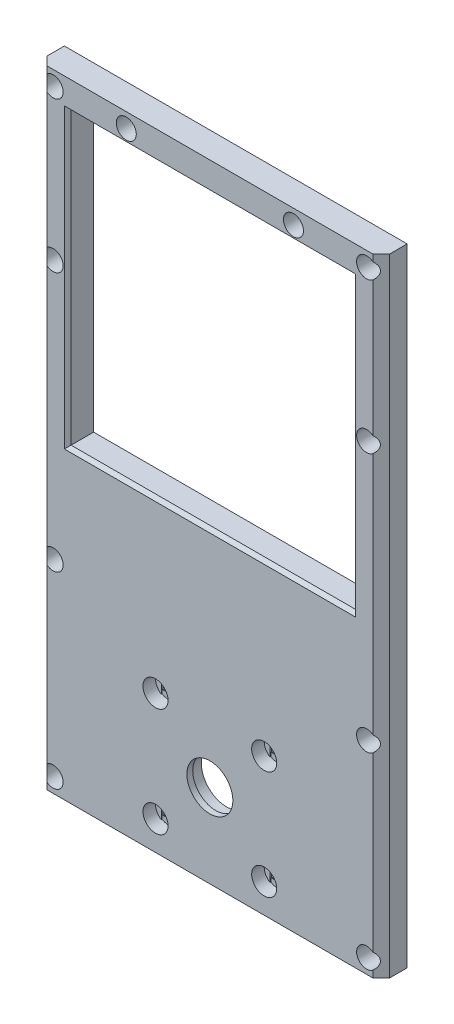
SolidWorks part; units mm, degrees
ref_plane "Front Plane" through (0, 0, 0) normal (0, 0, 1) x (1, 0, 0)
ref_plane "Top Plane" through (0, 0, 0) normal (0, 1, 0) x (1, 0, 0)
ref_plane "Right Plane" through (0, 0, 0) normal (1, 0, 0) x (0, 0, -1)
sketch "Sketch1" plane through (0, 0, 0) normal (0, 0, 1) x (1, 0, 0)
  line L1 (-41, -75) -> (41, -75)
  line L2 (-41, -75) -> (-41, 75)
  line L3 (-41, 75) -> (41, 75)
  line L4 (41, -75) -> (41, 75)
  line L5 (-41, -75) -> (41, 75) construction
  line L6 (-41, 75) -> (41, -75) construction
  line L7 (-34, -68) -> (34, -68)
  line L8 (-34, -68) -> (-34, 68)
  line L9 (-34, 68) -> (34, 68)
  line L10 (34, -68) -> (34, 68)
  line L11 (-34, -68) -> (34, 68) construction
  line L12 (-34, 68) -> (34, -68) construction
  point P0 (0, 0)
  point P6 (0, 0)
  dimension "D1" = 150
  dimension "D2" = 82
  dimension "D3" = 7
  dimension "D4" = 7
extrude "Boss-Extrude1" add sketch "Sketch1" along normal blind 7
sketch "Sketch2" plane through (0, 0, 7) normal (0, 0, 1) x (1, 0, 0)
  line L0 (34, -68) -> (34, 68) construction
  line L1 (-34, -68) -> (34, -68)
  line L2 (-34, -68) -> (-34, -32)
  line L3 (-34, -32) -> (34, -32)
  line L4 (34, -68) -> (34, -32)
  dimension "D1" = 36
extrude "Boss-Extrude2" add sketch "Sketch2" against normal up to surface (7 mm away) up to face at (0, 0, 0)
sketch "Sketch3" plane through (0, 0, 0) normal (0, 0, -1) x (-1, 0, 0)
  line L0 (0, -75) -> (0, -55) construction
  line L1 (41, -75) -> (-41, -75) construction
  circle A0 centre (0, -55) radius 5.5
  dimension "D1" = 11
  dimension "D2" = 20
extrude "Cut-Extrude1" cut sketch "Sketch3" against normal through all
sketch "Sketch4" plane through (0, 0, 0) normal (0, 0, -1) x (-1, 0, 0)
  circle A0 centre (0, -55) radius 6.05
  dimension "D1" = 12.1
extrude "Cut-Extrude2" cut sketch "Sketch4" against normal offset from surface (5.6 mm away) 1.4 up to face at (-5.5, -55, 7)
sketch "Sketch5" plane through (0, 0, 0) normal (0, 0, -1) x (-1, 0, 0)
  circle A0 centre (0, -55) radius 11
  dimension "D1" = 22
extrude "Cut-Extrude3" cut sketch "Sketch5" against normal offset from surface (3 mm away) 2.6 up to face at (-6.05, -55, 5.6)
sketch "Sketch6" plane through (0, 0, 0) normal (0, 0, -1) x (-1, 0, 0)
  line L1 (-13, -68) -> (13, -68) construction
  line L2 (-13, -68) -> (-13, -42) construction
  line L3 (-13, -42) -> (13, -42) construction
  line L4 (13, -68) -> (13, -42) construction
  line L5 (-13, -68) -> (13, -42) construction
  line L6 (-13, -42) -> (13, -68) construction
  circle A0 centre (-13, -42) radius 1.6
  circle A1 centre (13, -42) radius 1.6
  circle A2 centre (13, -68) radius 1.6
  circle A3 centre (-13, -68) radius 1.6
  point P0 (0, -55)
  dimension "D2" = 3.2
  dimension "D1" = 26
extrude "Cut-Extrude4" cut sketch "Sketch6" against normal through all
sketch "Sketch7" plane through (0, 0, 0) normal (0, 0, -1) x (-1, 0, 0)
  line L1 (-25, -74) -> (25, -74)
  line L2 (-25, -74) -> (-25, -36)
  line L3 (-25, -36) -> (25, -36)
  line L4 (25, -74) -> (25, -36)
  line L5 (-25, -74) -> (25, -36) construction
  line L6 (-25, -36) -> (25, -74) construction
  point P0 (0, -55)
  dimension "D1" = 50
  dimension "D2" = 38
extrude "Cut-Extrude5" cut sketch "Sketch7" against normal blind 1
sketch "Sketch8" plane through (0, 0, 7) normal (0, 0, 1) x (1, 0, 0)
  circle A0 centre (-13, -42) radius 3
  circle A1 centre (13, -42) radius 3
  circle A2 centre (13, -68) radius 3
  circle A3 centre (-13, -68) radius 3
  dimension "D1" = 6
extrude "Cut-Extrude6" cut sketch "Sketch8" against normal blind 3
sketch "Sketch9" plane through (0, 0, 7) normal (0, 0, 1) x (1, 0, 0)
  line L0 (-41, 75) -> (-41, -75) construction
  line L1 (-37.5, -71.5) -> (37.5, -71.5) construction
  line L2 (-37.5, -71.5) -> (-37.5, 71.5) construction
  line L3 (-37.5, 71.5) -> (37.5, 71.5) construction
  line L4 (37.5, -71.5) -> (37.5, 71.5) construction
  line L5 (-37.5, -71.5) -> (37.5, 71.5) construction
  line L6 (-37.5, 71.5) -> (37.5, -71.5) construction
  line L7 (41, 75) -> (-41, 75) construction
  circle A0 centre (-37.5, 71.5) radius 1.35
  circle A1 centre (37.5, 71.5) radius 1.35
  circle A4 centre (-37.5, -71.5) radius 1.35
  circle A5 centre (37.5, -71.5) radius 1.35
  circle A6 centre (-37.5, 35.5) radius 1.35
  circle A7 centre (37.5, 35.5) radius 1.35
  circle A8 centre (37.5, -26.5) radius 1.35
  circle A9 centre (-37.5, -26.5) radius 1.35
  point P0 (0, 0)
  dimension "D3" = 2.7
  dimension "D1" = 3.5
  dimension "D2" = 3.5
  dimension "D4" = 45
  dimension "D5" = 36
extrude "Cut-Extrude7" cut sketch "Sketch9" against normal through all
sketch "Sketch10" plane through (0, 0, 7) normal (0, 0, 1) x (1, 0, 0)
  circle A0 centre (-37.5, 71.5) radius 2.4
  circle A1 centre (37.5, 35.5) radius 2.4
  circle A2 centre (-37.5, 35.5) radius 2.4
  circle A3 centre (37.5, 71.5) radius 2.4
  circle A4 centre (-37.5, -71.5) radius 2.4
  circle A5 centre (37.5, -71.5) radius 2.4
  circle A6 centre (-37.5, -26.5) radius 2.4
  circle A7 centre (37.5, -26.5) radius 2.4
  dimension "D1" = 4.8
extrude "Cut-Extrude8" cut sketch "Sketch10" against normal blind 5
chamfer "Chamfer1" distance 2 angle 45 2 edges at (-41, 0, 7) (41, 0, 7)
sketch "Sketch11" plane through (0, 0, 7) normal (0, 0, 1) x (1, 0, 0)
  line L0 (34, -32) -> (34, 68) construction
  line L1 (-34, -32) -> (34, -32)
  line L2 (-34, -32) -> (-34, -1.5)
  line L3 (-34, -1.5) -> (34, -1.5)
  line L4 (34, -32) -> (34, -1.5)
  line L5 (-39, -75) -> (39, -75) construction
  dimension "D1" = 73.5
extrude "Boss-Extrude3" add sketch "Sketch11" against normal up to surface (7 mm away) up to face at (-36.15, -71.5, 0)
sketch "Sketch12" plane through (0, 0, 7) normal (0, 0, 1) x (1, 0, 0)
  line L0 (-37.5, 71.5) -> (37.5, 71.5) construction
  line L1 (-20, 71.5) -> (20, 71.5) construction
  circle A0 centre (-20, 71.5) radius 1.35
  circle A1 centre (20, 71.5) radius 1.35
  circle A2 centre (-37.5, 71.5) radius 1.35 construction
  point P7 (0, 71.5)
  dimension "D1" = 40
extrude "Cut-Extrude9" cut sketch "Sketch12" against normal through all
sketch "Sketch13" plane through (0, 0, 7) normal (0, 0, 1) x (1, 0, 0)
  circle A0 centre (-20, 71.5) radius 2.4
  circle A1 centre (20, 71.5) radius 2.4
  circle A2 centre (-37.5, 71.5) radius 2.4 construction
extrude "Cut-Extrude10" cut sketch "Sketch13" against normal up to surface (5 mm away) up to face at (-35.1, 71.5, 2)
chamfer "Chamfer2" distance 0.8 angle 45 12 edges at (0, -75, 0) (-41, 0, 0) (0, 75, 0) (41, 0, 0) (34, 33.25, 7) (0, 68, 7) (-34, 33.25, 7) (0, -1.5, 7) (-34, 33.25, 0) (0, 68, 0) (34, 33.25, 0) (0, -1.5, 0)
sketch "Sketch14" plane through (0, 0, 2) normal (0, 0, 1) x (1, 0, 0)
  line L2 (-38.85, -28.4843) -> (-38.85, -24.5157)
  line L4 (-36.15, -28.4843) -> (-36.15, -24.5157)
  line L5 (-38.85, -28.4843) -> (-36.15, -24.5157) construction
  line L6 (-38.85, -24.5157) -> (-36.15, -28.4843) construction
  line L14 (-38.85, -73.4843) -> (-38.85, -69.5157)
  line L16 (-36.15, -73.4843) -> (-36.15, -69.5157)
  line L17 (-38.85, -73.4843) -> (-36.15, -69.5157) construction
  line L18 (-38.85, -69.5157) -> (-36.15, -73.4843) construction
  line L26 (-38.85, 33.5157) -> (-38.85, 37.4843)
  line L28 (-36.15, 33.5157) -> (-36.15, 37.4843)
  line L29 (-38.85, 33.5157) -> (-36.15, 37.4843) construction
  line L30 (-38.85, 37.4843) -> (-36.15, 33.5157) construction
  line L32 (-21.35, 69.5157) -> (-21.35, 73.4843)
  line L34 (-18.65, 69.5157) -> (-18.65, 73.4843)
  line L35 (-21.35, 69.5157) -> (-18.65, 73.4843) construction
  line L36 (-21.35, 73.4843) -> (-18.65, 69.5157) construction
  line L38 (-38.85, 69.5157) -> (-38.85, 73.4843)
  line L40 (-36.15, 69.5157) -> (-36.15, 73.4843)
  line L41 (-38.85, 69.5157) -> (-36.15, 73.4843) construction
  line L42 (-38.85, 73.4843) -> (-36.15, 69.5157) construction
  arc A0 (-39, -28.3735) -> (-39, -24.6265) centre (-37.5, -26.5) ccw construction
  circle A2 centre (-37.5, -71.5) radius 2.4 construction
  circle A4 centre (-37.5, 35.5) radius 2.4 construction
  circle A5 centre (-20, 71.5) radius 2.4 construction
  circle A6 centre (-37.5, 71.5) radius 2.4 construction
  circle A7 centre (-37.5, 71.5) radius 1.35 construction
  circle A8 centre (-20, 71.5) radius 1.35 construction
  circle A9 centre (-37.5, 35.5) radius 1.35 construction
  circle A10 centre (-37.5, -26.5) radius 1.35 construction
  circle A12 centre (-37.5, -71.5) radius 1.35 construction
  arc A16 (-21.35, 69.5157) -> (-18.65, 69.5157) centre (-20, 71.5) ccw
  arc A17 (-36.15, 73.4843) -> (-38.85, 73.4843) centre (-37.5, 71.5) ccw
  arc A18 (-36.15, 37.4843) -> (-38.85, 37.4843) centre (-37.5, 35.5) ccw
  arc A20 (-38.85, -28.4843) -> (-36.15, -28.4843) centre (-37.5, -26.5) ccw
  arc A22 (-36.15, -69.5157) -> (-38.85, -69.5157) centre (-37.5, -71.5) ccw
  arc A23 (-38.85, 69.5157) -> (-36.15, 69.5157) centre (-37.5, 71.5) ccw
  arc A24 (-18.65, 73.4843) -> (-21.35, 73.4843) centre (-20, 71.5) ccw
  arc A25 (-38.85, 33.5157) -> (-36.15, 33.5157) centre (-37.5, 35.5) ccw
  arc A26 (-36.15, -24.5157) -> (-38.85, -24.5157) centre (-37.5, -26.5) ccw
  arc A29 (-38.85, -73.4843) -> (-36.15, -73.4843) centre (-37.5, -71.5) ccw
  point P0 (-37.5, -26.5)
  point P17 (-37.5, -71.5)
  point P33 (-37.5, 35.5)
  point P41 (-20, 71.5)
  point P49 (-37.5, 71.5)
extrude "Cut-Extrude11" cut sketch "Sketch14" against normal blind 0.2
sketch "Sketch15" plane through (0, 0, 1.8) normal (0, 0, 1) x (1, 0, 0)
  line L0 (-36.15, -71.5) -> (-36.15, -69.5157) construction
  line L1 (-38.85, -72.85) -> (-36.15, -72.85)
  line L2 (-38.85, -72.85) -> (-38.85, -70.15)
  line L3 (-38.85, -70.15) -> (-36.15, -70.15)
  line L4 (-36.15, -72.85) -> (-36.15, -70.15)
  line L5 (-38.85, -72.85) -> (-36.15, -70.15) construction
  line L6 (-38.85, -70.15) -> (-36.15, -72.85) construction
  line L7 (-36.15, 35.5) -> (-36.15, 37.4843) construction
  line L8 (-38.85, -27.85) -> (-36.15, -27.85)
  line L9 (-38.85, -27.85) -> (-38.85, -25.15)
  line L10 (-38.85, -25.15) -> (-36.15, -25.15)
  line L11 (-36.15, -27.85) -> (-36.15, -25.15)
  line L12 (-38.85, -27.85) -> (-36.15, -25.15) construction
  line L13 (-38.85, -25.15) -> (-36.15, -27.85) construction
  line L14 (-38.85, 34.15) -> (-36.15, 34.15)
  line L15 (-38.85, 34.15) -> (-38.85, 36.85)
  line L16 (-38.85, 36.85) -> (-36.15, 36.85)
  line L17 (-36.15, 34.15) -> (-36.15, 36.85)
  line L18 (-38.85, 34.15) -> (-36.15, 36.85) construction
  line L19 (-38.85, 36.85) -> (-36.15, 34.15) construction
  line L20 (-36.15, 69.5157) -> (-36.15, 73.4843) construction
  line L21 (-38.85, 70.15) -> (-36.15, 70.15)
  line L22 (-38.85, 70.15) -> (-38.85, 72.85)
  line L23 (-38.85, 72.85) -> (-36.15, 72.85)
  line L24 (-36.15, 70.15) -> (-36.15, 72.85)
  line L25 (-38.85, 70.15) -> (-36.15, 72.85) construction
  line L26 (-38.85, 72.85) -> (-36.15, 70.15) construction
  line L27 (-18.65, 69.5157) -> (-18.65, 73.4843) construction
  line L28 (-21.35, 70.15) -> (-18.65, 70.15)
  line L29 (-21.35, 70.15) -> (-21.35, 72.85)
  line L30 (-21.35, 72.85) -> (-18.65, 72.85)
  line L31 (-18.65, 70.15) -> (-18.65, 72.85)
  line L32 (-21.35, 70.15) -> (-18.65, 72.85) construction
  line L33 (-21.35, 72.85) -> (-18.65, 70.15) construction
  arc A0 (-36.15, -26.5) -> (-38.85, -26.5) centre (-37.5, -26.5) ccw construction
  arc A1 (-36.15, 35.5) -> (-38.85, 35.5) centre (-37.5, 35.5) ccw construction
  arc A2 (-18.65, 71.5) -> (-21.35, 71.5) centre (-20, 71.5) ccw construction
  arc A3 (-36.15, 71.5) -> (-38.85, 71.5) centre (-37.5, 71.5) ccw construction
  point P0 (-37.5, -71.5)
  point P8 (-37.5, -26.5)
  point P17 (-37.5, 35.5)
  point P28 (-37.5, 71.5)
  point P36 (-20, 71.5)
extrude "Cut-Extrude12" cut sketch "Sketch15" against normal blind 0.2
sketch "Sketch16" plane through (0, 0, 4) normal (0, 0, 1) x (1, 0, 0)
  line L2 (-14.6, -44.5377) -> (-14.6, -39.4623)
  line L4 (-11.4, -44.5377) -> (-11.4, -39.4623)
  line L5 (-14.6, -44.5377) -> (-11.4, -39.4623) construction
  line L6 (-14.6, -39.4623) -> (-11.4, -44.5377) construction
  line L8 (-14.6, -70.5377) -> (-14.6, -65.4623)
  line L10 (-11.4, -70.5377) -> (-11.4, -65.4623)
  line L11 (-14.6, -70.5377) -> (-11.4, -65.4623) construction
  line L12 (-14.6, -65.4623) -> (-11.4, -70.5377) construction
  circle A0 centre (-13, -42) radius 3 construction
  circle A1 centre (-13, -68) radius 3 construction
  circle A2 centre (-13, -68) radius 1.6 construction
  circle A3 centre (-13, -42) radius 1.6 construction
  circle A4 centre (-13, -68) radius 3 construction
  circle A5 centre (-13, -42) radius 3 construction
  arc A6 (-11.4, -65.4623) -> (-14.6, -65.4623) centre (-13, -68) ccw
  arc A7 (-14.6, -44.5377) -> (-11.4, -44.5377) centre (-13, -42) ccw
  arc A8 (-11.4, -39.4623) -> (-14.6, -39.4623) centre (-13, -42) ccw
  arc A9 (-14.6, -70.5377) -> (-11.4, -70.5377) centre (-13, -68) ccw
  point P0 (-13, -42)
  point P8 (-13, -68)
extrude "Cut-Extrude13" cut sketch "Sketch16" against normal blind 0.2
sketch "Sketch17" plane through (0, 0, 3.8) normal (0, 0, 1) x (1, 0, 0)
  line L0 (-11.4, -44.5377) -> (-11.4, -39.4623) construction
  line L1 (-14.6, -43.6) -> (-11.4, -43.6)
  line L2 (-14.6, -43.6) -> (-14.6, -40.4)
  line L3 (-14.6, -40.4) -> (-11.4, -40.4)
  line L4 (-11.4, -43.6) -> (-11.4, -40.4)
  line L5 (-14.6, -43.6) -> (-11.4, -40.4) construction
  line L6 (-14.6, -40.4) -> (-11.4, -43.6) construction
  line L7 (-11.4, -70.5377) -> (-11.4, -65.4623) construction
  line L8 (-14.6, -69.6) -> (-11.4, -69.6)
  line L9 (-14.6, -69.6) -> (-14.6, -66.4)
  line L10 (-14.6, -66.4) -> (-11.4, -66.4)
  line L11 (-11.4, -69.6) -> (-11.4, -66.4)
  line L12 (-14.6, -69.6) -> (-11.4, -66.4) construction
  line L13 (-14.6, -66.4) -> (-11.4, -69.6) construction
  arc A0 (-11.4, -68) -> (-14.6, -68) centre (-13, -68) ccw construction
  arc A1 (-11.4, -42) -> (-14.6, -42) centre (-13, -42) ccw construction
  point P0 (-13, -42)
  point P8 (-13, -68)
extrude "Cut-Extrude14" cut sketch "Sketch17" against normal blind 0.2
mirror "Mirror1" about plane through (0, 0, 0) normal (1, 0, 0) of "Cut-Extrude12", "Cut-Extrude13", "Cut-Extrude14", "Cut-Extrude11"
